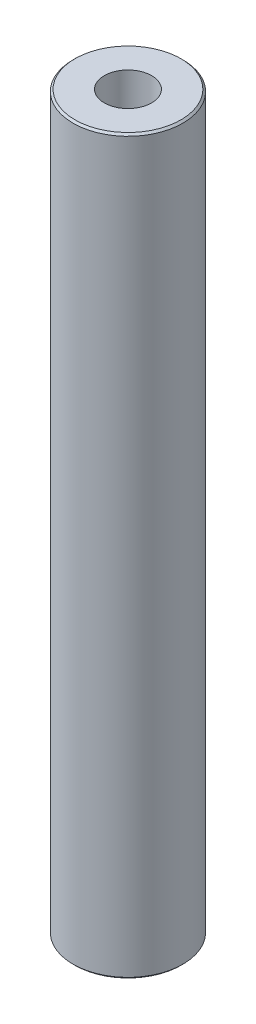
SolidWorks part; units mm, degrees
ref_plane "Front Plane" through (0, 0, 0) normal (0, 0, 1) x (1, 0, 0)
ref_plane "Top Plane" through (0, 0, 0) normal (0, 1, 0) x (1, 0, 0)
ref_plane "Right Plane" through (0, 0, 0) normal (1, 0, 0) x (0, 0, -1)
sketch "Sketch1" plane through (0, 0, 0) normal (0, 1, 0) x (1, 0, 0)
  circle A0 centre (0, 0) radius 45
  dimension "SHAFT_OD" = 90
extrude "Boss-Extrude1" add sketch "Sketch1" along normal blind 600
sketch "Sketch2" plane through (0, 0, 0) normal (0, 1, 0) x (1, 0, 0)
  circle A0 centre (0, 0) radius 19.3966
  dimension "BORE_D" = 38.7933
extrude "Cut-Extrude1" cut sketch "Sketch2" along normal through all
chamfer "Chamfer1" distance 1.5808 angle 45 2 edges at (0, 600, 45) (0, 0, 45)
